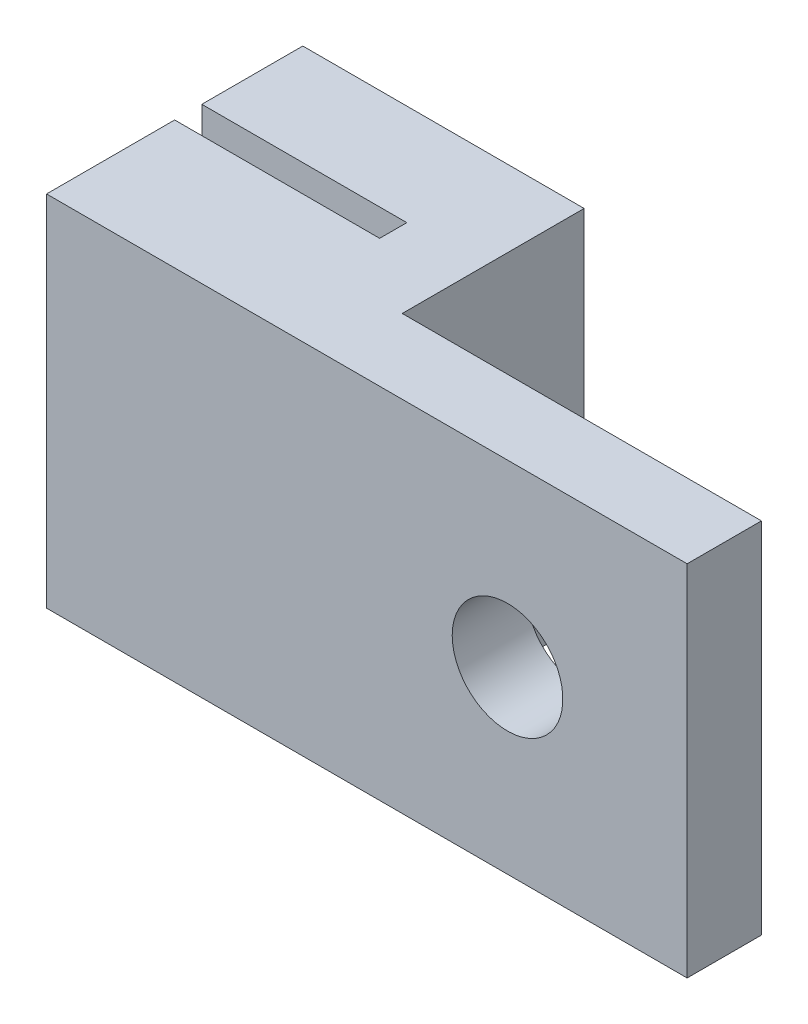
SolidWorks part; units mm, degrees
ref_plane "Front Plane" through (0, 0, 0) normal (0, 0, 1) x (1, 0, 0)
ref_plane "Top Plane" through (0, 0, 0) normal (0, 1, 0) x (1, 0, 0)
ref_plane "Right Plane" through (0, 0, 0) normal (1, 0, 0) x (0, 0, -1)
sketch "Sketch1" plane through (0, 0, 0) normal (0, 1, 0) x (1, 0, 0)
  line L1 (-1237.7101, -397.7364) -> (-1212.7101, -397.7364)
  line L2 (-1237.7101, -397.7364) -> (-1237.7101, -387.7364)
  line L3 (-1237.7101, -387.7364) -> (-1212.7101, -387.7364)
  line L4 (-1212.7101, -397.7364) -> (-1212.7101, -387.7364)
  line L5 (-1237.7101, -391.6764) -> (-1229.7101, -391.6764)
  line L6 (-1237.7101, -391.6764) -> (-1237.7101, -392.7364)
  line L7 (-1237.7101, -392.7364) -> (-1229.7101, -392.7364)
  line L8 (-1229.7101, -391.6764) -> (-1229.7101, -392.7364)
  dimension "D1" = 5
  dimension "D2" = 25
  dimension "D3" = 8
  dimension "D4" = 1.06
  dimension "D5" = 10
extrude "Boss-Extrude1" add sketch "Sketch1" against normal blind 14 contours L5 L8 L7 L2 L1 L4 L3 region at (-1224.9117, 0, 392.755)
sketch "Sketch2" plane through (0, 0, 0) normal (0, 1, 0) x (1, 0, 0)
  line L0 (-1237.7101, -387.7364) -> (-1212.7101, -387.7364) construction
  line L1 (-1226.7298, -387.7364) -> (-1212.7101, -387.7364)
  line L2 (-1226.7298, -387.7364) -> (-1226.7298, -394.836)
  line L3 (-1226.7298, -394.836) -> (-1212.7101, -394.836)
  line L4 (-1212.7101, -387.7364) -> (-1212.7101, -394.836)
  line L5 (-1212.7101, -397.7364) -> (-1212.7101, -387.7364) construction
extrude "Cut-Extrude1" cut sketch "Sketch2" against normal through all
sketch "Sketch4" plane through (0, 0, 394.836) normal (0, 0, -1) x (-1, 0, 0)
  line L0 (1226.7298, 0) -> (1212.7101, 0) construction
  line L1 (1219.72, 0) -> (1219.72, -14) construction
  line L2 (1226.7298, -14) -> (1212.7101, -14) construction
  line L3 (1212.7101, -7) -> (1226.7298, -7) construction
  line L4 (1212.7101, -14) -> (1212.7101, 0) construction
  line L5 (1226.7298, -14) -> (1226.7298, 0) construction
  circle A0 centre (1219.72, -7) radius 2.159
  dimension "D1" = 4.318
extrude "Cut-Extrude2" cut sketch "Sketch4" against normal through all
